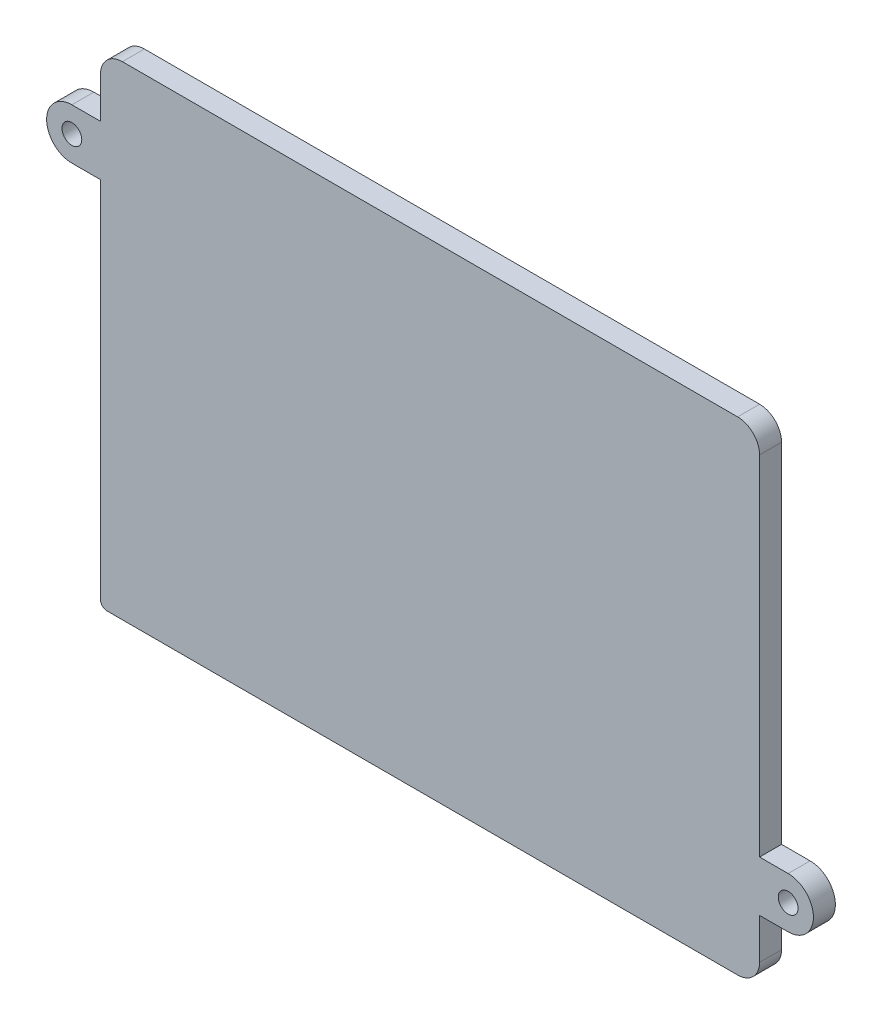
SolidWorks part; units mm, degrees
ref_plane "Front Plane" through (0, 0, 0) normal (0, 0, 1) x (1, 0, 0)
ref_plane "Top Plane" through (0, 0, 0) normal (0, 1, 0) x (1, 0, 0)
ref_plane "Right Plane" through (0, 0, 0) normal (1, 0, 0) x (0, 0, -1)
sketch "Sketch1" plane through (0, 0, 0) normal (0, 0, 1) x (1, 0, 0)
  line L43 (70, 6) -> (70, 2) construction
  line L44 (70, 2) -> (75, 2) construction
  line L46 (75, 2) -> (75, 6) construction
  line L48 (75, 6) -> (70, 6) construction
  line L49 (70, 26) -> (70, 6) construction
  line L52 (70, 6) -> (75, 6) construction
  line L53 (75, 6) -> (75, 26) construction
  line L56 (75, 26) -> (70, 26) construction
  line L75 (70, 30) -> (70, 26) construction
  line L76 (70, 26) -> (75, 26) construction
  line L77 (75, 26) -> (75, 30) construction
  line L78 (75, 30) -> (70, 30) construction
  line L79 (75, 2) -> (70, 2) construction
  line L80 (70, 2) -> (70, -45) construction
  line L81 (65, -50) -> (-65, -50) construction
  line L82 (-70, -45) -> (-70, 45) construction
  line L83 (-65, 50) -> (65, 50) construction
  line L84 (70, 45) -> (70, 30) construction
  line L85 (70, 30) -> (75, 30) construction
  line L86 (75, 30) -> (75, 50) construction
  line L87 (70, 55) -> (-70, 55) construction
  line L88 (-75, 50) -> (-75, 40.75) construction
  line L89 (-75, 40.75) -> (-81.5, 40.75) construction
  line L90 (-81.5, 29.25) -> (-75, 29.25) construction
  line L91 (-75, 29.25) -> (-75, -53.5) construction
  line L92 (-73.5, -55) -> (70, -55) construction
  line L93 (75, -50) -> (75, -40.75) construction
  line L94 (75, -40.75) -> (81.5, -40.75) construction
  line L95 (81.5, -29.25) -> (75, -29.25) construction
  line L96 (75, -29.25) -> (75, 2) construction
  line L97 (70, 6) -> (70, 2)
  line L98 (70, 2) -> (75, 2)
  line L99 (75, 2) -> (75, 6)
  line L100 (75, 6) -> (70, 6)
  line L101 (70, 26) -> (70, 6)
  line L102 (70, 6) -> (75, 6)
  line L104 (75, 6) -> (75, 26)
  line L105 (75, 26) -> (70, 26)
  line L106 (70, 30) -> (70, 26)
  line L107 (70, 26) -> (75, 26)
  line L110 (75, 26) -> (75, 30)
  line L112 (75, 30) -> (70, 30)
  line L113 (75, 2) -> (70, 2)
  line L114 (70, 2) -> (70, -45)
  line L115 (65, -50) -> (-65, -50)
  line L117 (-70, -45) -> (-70, 45)
  line L118 (-65, 50) -> (65, 50)
  line L138 (70, 45) -> (70, 30)
  line L139 (70, 30) -> (75, 30)
  line L140 (75, 30) -> (75, 50)
  line L141 (70, 55) -> (-70, 55)
  line L142 (-75, 50) -> (-75, 40.75)
  line L143 (-75, 40.75) -> (-81.5, 40.75)
  line L144 (-81.5, 29.25) -> (-75, 29.25)
  line L145 (-75, 29.25) -> (-75, -53.5)
  line L146 (-73.5, -55) -> (70, -55)
  line L147 (75, -50) -> (75, -40.75)
  line L148 (75, -40.75) -> (81.5, -40.75)
  line L149 (81.5, -29.25) -> (75, -29.25)
  line L150 (75, -29.25) -> (75, 2)
  circle A4 centre (81.5, -35) radius 2.25 construction
  circle A29 centre (81.5, -35) radius 2.25
  arc A34 (65, -50) -> (70, -45) centre (65, -45) ccw construction
  arc A35 (-70, -45) -> (-65, -50) centre (-65, -45) ccw construction
  arc A36 (-65, 50) -> (-70, 45) centre (-65, 45) ccw construction
  arc A37 (70, 45) -> (65, 50) centre (65, 45) ccw construction
  arc A38 (75, 50) -> (70, 55) centre (70, 50) ccw construction
  arc A39 (-70, 55) -> (-75, 50) centre (-70, 50) ccw construction
  arc A40 (-81.5, 40.75) -> (-87.25, 35) centre (-81.5, 35) ccw construction
  arc A41 (-87.25, 35) -> (-81.5, 29.25) centre (-81.5, 35) ccw construction
  arc A42 (-75, -53.5) -> (-73.5, -55) centre (-73.5, -53.5) ccw construction
  arc A43 (70, -55) -> (75, -50) centre (70, -50) ccw construction
  arc A44 (81.5, -40.75) -> (87.25, -35) centre (81.5, -35) ccw construction
  arc A45 (87.25, -35) -> (81.5, -29.25) centre (81.5, -35) ccw construction
  circle A47 centre (-81.5, 35) radius 2.25 construction
  arc A49 (65, -50) -> (70, -45) centre (65, -45) ccw
  arc A50 (-70, -45) -> (-65, -50) centre (-65, -45) ccw
  arc A51 (-65, 50) -> (-70, 45) centre (-65, 45) ccw
  arc A58 (70, 45) -> (65, 50) centre (65, 45) ccw
  arc A61 (75, 50) -> (70, 55) centre (70, 50) ccw
  arc A71 (-70, 55) -> (-75, 50) centre (-70, 50) ccw
  arc A72 (-81.5, 40.75) -> (-87.25, 35) centre (-81.5, 35) ccw
  arc A73 (-87.25, 35) -> (-81.5, 29.25) centre (-81.5, 35) ccw
  arc A74 (-75, -53.5) -> (-73.5, -55) centre (-73.5, -53.5) ccw
  arc A75 (70, -55) -> (75, -50) centre (70, -50) ccw
  arc A76 (81.5, -40.75) -> (87.25, -35) centre (81.5, -35) ccw
  arc A77 (87.25, -35) -> (81.5, -29.25) centre (81.5, -35) ccw
  circle A79 centre (-81.5, 35) radius 2.25
extrude "Boss-Extrude1" add sketch "Sketch1" along normal blind 5 contours L97 | L97 | A76 A77 L149 L150 L98 L114 A49 L115 A50 L117 A51 L118 A58 L138 L112 L140 A61 L141 A71 L142 L143 A72 A73 L144 L145 A74 L146 A75 L147 L148 A79 | L110 L112 L106 L105 | L104 L105 L101 L100 region at (72.5, 4, 0) region at (72.5, 16, 0) region at (0, 0, 0) region at (72.5, -0.0628, 0) region at (72.5, 28, 0)
sketch "Sketch3" plane through (0, 0, 0) normal (0, 0, 1) x (1, 0, 0)
  line L8 (-65, -50) -> (65, -50)
  line L9 (70, -45) -> (70, 45)
  line L10 (-65, 50) -> (65, 50)
  line L11 (-70, 45) -> (-70, -45)
  line L12 (-68.5, 45) -> (-68.5, -45)
  line L13 (-65, -48.5) -> (65, -48.5)
  line L14 (68.5, -45) -> (68.5, 45)
  line L15 (-65, 48.5) -> (65, 48.5)
  arc A0 (70, 45) -> (65, 50) centre (65, 45) ccw construction
  arc A1 (65, -50) -> (70, -45) centre (65, -45) ccw construction
  arc A3 (-70, -45) -> (-65, -50) centre (-65, -45) ccw construction
  arc A12 (-65, 50) -> (-70, 45) centre (-65, 45) ccw construction
  arc A13 (70, 45) -> (65, 50) centre (65, 45) ccw
  arc A16 (65, -50) -> (70, -45) centre (65, -45) ccw
  arc A19 (-70, -45) -> (-65, -50) centre (-65, -45) ccw
  arc A20 (-65, 50) -> (-70, 45) centre (-65, 45) ccw
  arc A21 (-68.5, -45) -> (-65, -48.5) centre (-65, -45) ccw
  arc A22 (65, -48.5) -> (68.5, -45) centre (65, -45) ccw
  arc A23 (68.5, 45) -> (65, 48.5) centre (65, 45) ccw
  arc A24 (-65, 48.5) -> (-68.5, 45) centre (-65, 45) ccw
  dimension "D1" = 1.5
extrude "Boss-Extrude2" add sketch "Sketch3" against normal blind 2 contours L12 A24 L15 A23 L14 A22 L13 A21 region at (0, 0, 0)
